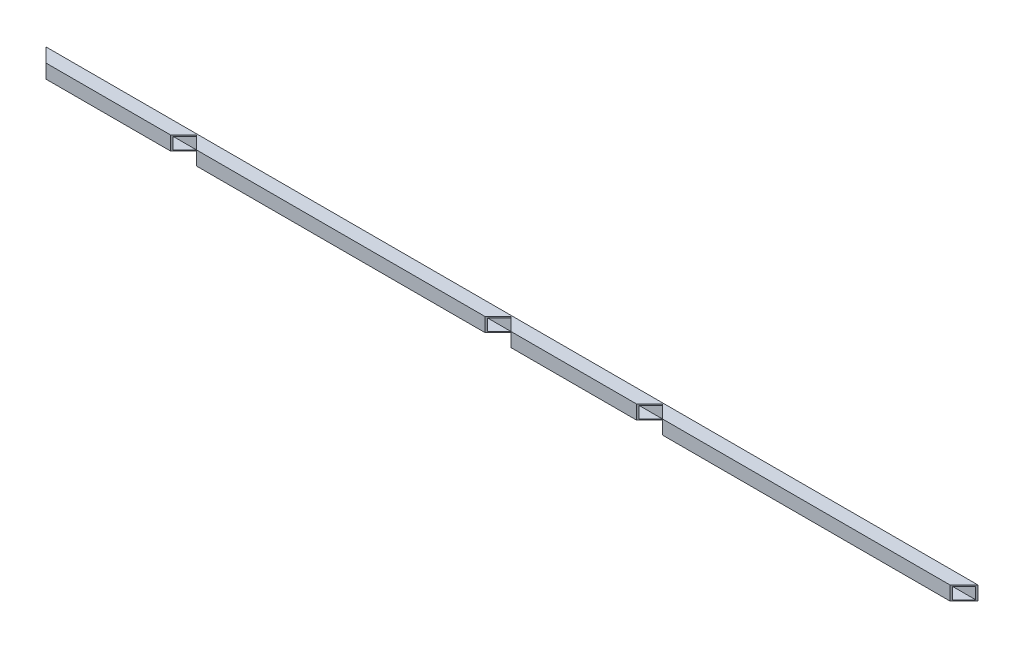
SolidWorks part; units mm, degrees
ref_plane "Front Plane" through (0, 0, 0) normal (0, 0, 1) x (1, 0, 0)
ref_plane "Top Plane" through (0, 0, 0) normal (0, 1, 0) x (1, 0, 0)
ref_plane "Right Plane" through (0, 0, 0) normal (1, 0, 0) x (0, 0, -1)
sketch "Sketch4" plane through (0, 0, 0) normal (0, 1, 0) x (1, 0, 0)
  line L1 (-400, 6) -> (400, 6)
  line L2 (-400, 6) -> (-400, -6)
  line L3 (-400, -6) -> (400, -6)
  line L4 (400, 6) -> (400, -6)
  line L5 (-400, 6) -> (400, -6) construction
  line L6 (-400, -6) -> (400, 6) construction
  point P0 (0, 0)
  dimension "D1" = 800
  dimension "D2" = 12
base flange "Base-Flange1" sketch "Sketch4" thickness 12 reverse thickness direction no parameters "D1"=90
sketch "Sketch9" plane through (400, 0, 0) normal (1, 0, 0) x (0, 0, -1)
  line L0 (-6, -12) -> (6, -12) construction
  line L1 (-5, -1) -> (5, -1)
  line L2 (-5, -1) -> (-5, -11)
  line L3 (-5, -11) -> (5, -11)
  line L4 (5, -1) -> (5, -11)
  line L5 (-5, -1) -> (5, -11) construction
  line L6 (-5, -11) -> (5, -1) construction
  line L7 (6, -12) -> (6, 0) construction
  line L8 (-6, -12) -> (-6, 0) construction
  line L9 (-6, 0) -> (6, 0) construction
  point P0 (0, -6)
  dimension "D1" = 1
  dimension "D2" = 1
  dimension "D3" = 1
  dimension "D4" = 1
extrude "Cut-Extrude2" cut sketch "Sketch9" against normal through all normal cut yes
sketch "Sketch12" plane through (0, 0, 0) normal (0, 1, 0) x (1, 0, 0)
  line L0 (-270, 5) -> (-281, -6)
  line L1 (-400, -6) -> (400, -6) construction
  line L2 (-281, -6) -> (-259, -6)
  line L3 (-259, -6) -> (-270, 5)
  line L4 (400, 6) -> (-400, 6) construction
  line L5 (-400, 6) -> (-400, -6) construction
  line L6 (11, -6) -> (0, 5)
  line L7 (0, 5) -> (-11, -6)
  line L8 (-11, -6) -> (11, -6)
  line L12 (141, -6) -> (130, 5)
  line L13 (130, 5) -> (119, -6)
  line L14 (119, -6) -> (141, -6)
  line L15 (-140, 5) -> (-151, -6) [skipped]
  line L16 (-129, -6) -> (-140, 5) [skipped]
  line L17 (-151, -6) -> (-129, -6) [skipped]
  line L18 (-400, 6) -> (-388, -6)
  line L19 (-388, -6) -> (-400, -6)
  line L20 (-400, -6) -> (-400, 6)
  line L21 (400, -6) -> (400, 6)
  line L22 (400, 6) -> (388, -6)
  line L23 (388, -6) -> (400, -6)
  dimension "D1" = 1
  dimension "D2" = 130
  dimension "D3" = 2
  dimension "D4" = 2
extrude "Cut-Extrude3" cut sketch "Sketch12" against normal blind 72 normal cut yes
sketch "Sketch17" plane through (0, 0, -6) normal (0, 0, -1) x (-1, 0, 0)
  line L0 (0, -12) -> (0, 0)
  line L1 (-400, -12) -> (400, -12) construction
sketch "Bend-Lines1" [suppressed] plane through (0, 0, 0) normal (0, 1, 0) x (1, 0, 0)
sketch "Bounding-Box1" [suppressed] plane through (0, 0, 0) normal (0, 1, 0) x (1, 0, 0)
sheet metal parameters "Sheet-Metal3" thickness 12 parameters "D1"=90
flat pattern "Flat-Pattern3" [suppressed]
sketch "Bend-Lines2" plane through (0, 0, 0) normal (0, 1, 0) x (1, 0, 0)
sketch3d "Bounding-Box2" [suppressed]
  line L0 (-400, -6, 0) -> (400, -6, 0) construction
  line L1 (-400, 6, 0) -> (400, 6, 0) construction
  line L2 (-400, -6, 0) -> (-400, 6, 0) construction
  line L3 (400, -6, 0) -> (400, 6, 0) construction
sheet metal parameters "Sheet-Metal4" thickness 12 parameters "D1"=90
flat pattern "Flat-Pattern3"
sketch "Bend-Lines2" plane through (0, 0, 0) normal (0, 1, 0) x (1, 0, 0)
sketch3d "Bounding-Box2" [suppressed]
  line L0 (400, -6, 0) -> (-400, -6, 0) construction
  line L1 (400, 6, 0) -> (-400, 6, 0) construction
  line L2 (400, -6, 0) -> (400, 6, 0) construction
  line L3 (-400, -6, 0) -> (-400, 6, 0) construction
sheet metal parameters "Sheet-Metal5" thickness 12 parameters "D1"=90
flat pattern "Flat-Pattern3"
sketch "Bend-Lines2" plane through (0, 0, 0) normal (0, 1, 0) x (1, 0, 0)
sketch3d "Bounding-Box2" [suppressed]
  line L0 (400, -6, 0) -> (-400, -6, 0) construction
  line L1 (400, 6, 0) -> (-400, 6, 0) construction
  line L2 (400, -6, 0) -> (400, 6, 0) construction
  line L3 (-400, -6, 0) -> (-400, 6, 0) construction
